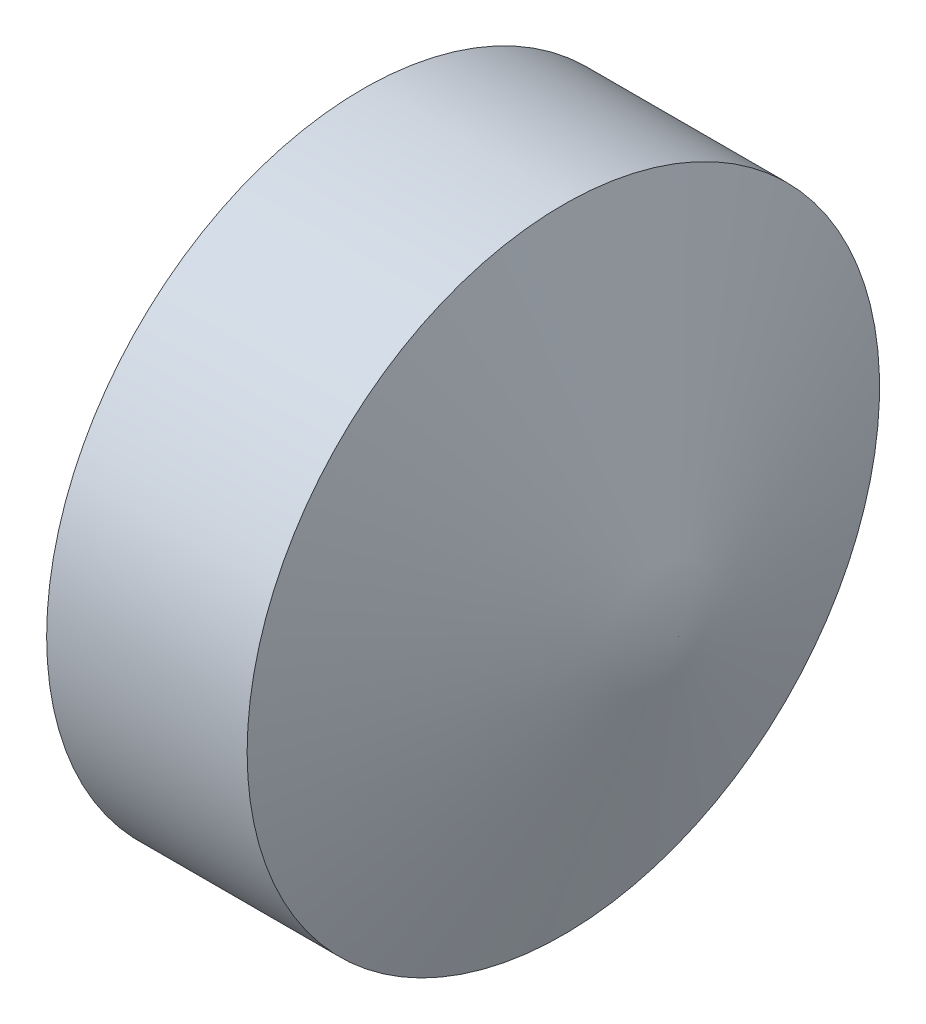
SolidWorks part; units mm, degrees
material "AISI 4340 Aço recozido"
ref_plane "Plano frontal" through (0, 0, 0) normal (0, 0, 1) x (1, 0, 0)
ref_plane "Plano superior" through (0, 0, 0) normal (0, 1, 0) x (1, 0, 0)
ref_plane "Plano direito" through (0, 0, 0) normal (1, 0, 0) x (0, 0, -1)
ref_plane "Plano1" through (0, 0, 0) normal (0, 0, -1) x (-1, 0, 0)
sketch "Esboço1" plane through (0, 0, 0) normal (0, 0, -1) x (-1, 0, 0)
  line L0 (-2.5063, 1.3563) -> (-3, 0)
  line L1 (-3, 0) -> (-1.5, 0)
  line L2 (-1.5, 0) -> (-1.5, 1.3563)
  line L3 (-1.5, 1.3563) -> (-2.5063, 1.3563)
  line L4 (-3, 0) -> (-1.5, 0) construction
  dimension "D1" = 70
  dimension "D2" = 1.5
revolve "Revolução1" add sketch "Esboço1" angle 360 about L4 reverse direction yes
sketch "Esboço2" plane through (1.5, 0, 0) normal (-1, 0, 0) x (0, 0, 1)
  line L0 (0.3753, -0.65) -> (0.7506, 0)
  line L1 (0.7506, 0) -> (0.3753, 0.65)
  line L2 (0.3753, 0.65) -> (-0.3753, 0.65)
  line L3 (-0.3753, 0.65) -> (-0.7506, 0)
  line L4 (-0.7506, 0) -> (-0.3753, -0.65)
  line L5 (-0.3753, -0.65) -> (0.3753, -0.65)
extrude "Corte-extrusão1" cut sketch "Esboço2" against normal blind 1.2
chamfer "Chanfro1" distance 0.2535 angle 30 1 edges at (1.5, 0, 1.3563) first distance on face at (1.5, 0, 0)
